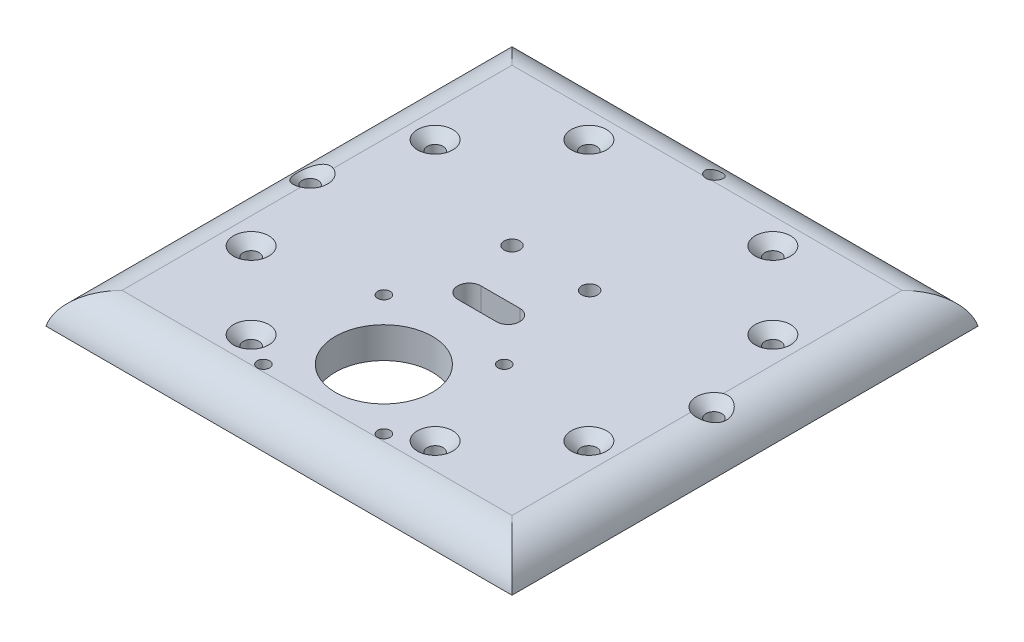
SolidWorks part; units mm, degrees
ref_plane "Front Plane" through (0, 0, 0) normal (0, 0, 1) x (1, 0, 0)
ref_plane "Top Plane" through (0, 0, 0) normal (0, 1, 0) x (1, 0, 0)
ref_plane "Right Plane" through (0, 0, 0) normal (1, 0, 0) x (0, 0, -1)
sketch "Sketch1" plane through (0, 0, 0) normal (0, 1, 0) x (1, 0, 0)
  line L0 (0, 0) -> (33.616, 0) construction
  line L8 (0, 0) -> (0, 37.386) construction
  line L9 (0, 37.386) -> (33.616, 0) construction
  line L18 (60, -60) -> (-60, -60)
  line L19 (60, -60) -> (60, 60)
  line L20 (60, 60) -> (-60, 60)
  line L21 (-60, -60) -> (-60, 60)
  line L22 (60, -60) -> (-60, 60) construction
  line L23 (60, 60) -> (-60, -60) construction
  circle A0 centre (0, 0) radius 60 construction
  dimension "D1" = 120
extrude "Boss-Extrude1" add sketch "Sketch1" along normal blind 8
sketch "Sketch2" plane through (0, 8, 0) normal (0, 1, 0) x (1, 0, 0)
  line L1 (15.5, -48.5) -> (-15.5, -48.5) construction
  line L2 (15.5, -48.5) -> (15.5, -17.5) construction
  line L3 (15.5, -17.5) -> (-15.5, -17.5) construction
  line L4 (-15.5, -48.5) -> (-15.5, -17.5) construction
  line L5 (15.5, -48.5) -> (-15.5, -17.5) construction
  line L6 (15.5, -17.5) -> (-15.5, -48.5) construction
  circle A0 centre (0, -33) radius 12.5
  circle A1 centre (-15.5, -48.5) radius 1.6
  circle A2 centre (15.5, -48.5) radius 1.6
  circle A3 centre (15.5, -17.5) radius 1.6
  circle A4 centre (-15.5, -17.5) radius 1.6
  dimension "D1" = 25
  dimension "D5" = 3.2
  dimension "D6" = 3.2
  dimension "D7" = 3.2
  dimension "D8" = 3.2
  dimension "D2" = 33
  dimension "D3" = 31
  dimension "D4" = 31
extrude "Cut-Extrude1" cut sketch "Sketch2" against normal through all
sketch "Sketch3" plane through (0, 8, 0) normal (0, 1, 0) x (1, 0, 0)
  line L0 (0, 0) -> (0, -60) construction
  line L1 (0, 0) -> (-33.5876, -33.5876) construction
  line L2 (-9.8995, 9.8995) -> (-43.4871, -23.6881) construction
  line L3 (9.8995, -9.8995) -> (-23.6881, -43.4871) construction
  circle A0 centre (0, 0) radius 60 construction
  circle A1 centre (-33.5876, -33.5876) radius 5 construction
  circle A2 centre (-43.4871, -23.6881) radius 2.05
  circle A3 centre (-23.6881, -43.4871) radius 2.05
  dimension "D5" = 4.1
  dimension "D6" = 4.1
  dimension "D7" = 10
  dimension "D1" = 45
  dimension "D2" = 47.5
  dimension "D3" = 14
  dimension "D4" = 14
extrude "Cut-Extrude2" cut sketch "Sketch3" against normal through all contours A2 | A3
pattern_circular "CirPattern1" count 4 over 360 about axis through (0, 0, 0) along (0, 1, 0) of "Cut-Extrude2"
sketch "Sketch4" plane through (0, 8, 0) normal (0, 1, 0) x (1, 0, 0)
  circle A0 centre (-52, 0) radius 2.05
  circle A1 centre (52, 0) radius 2.05
  circle A2 centre (0, 52) radius 2.05
  dimension "D3" = 4.1
  dimension "D4" = 4.1
  dimension "D6" = 4.1
  dimension "D1" = 52
  dimension "D2" = 52
  dimension "D5" = 52
extrude "Cut-Extrude3" cut sketch "Sketch4" against normal through all
sketch "Sketch5" plane through (0, 8, 0) normal (0, 1, 0) x (1, 0, 0)
  line L0 (-5, -6) -> (5, -6) construction
  line L1 (-5, -3) -> (5, -3)
  line L2 (-5, -9) -> (5, -9)
  circle A0 centre (-10, 10) radius 2.05
  circle A1 centre (10, 10) radius 2.05
  arc A2 (-5, -3) -> (-5, -9) centre (-5, -6) ccw
  arc A3 (5, -9) -> (5, -3) centre (5, -6) ccw
  point P6 (0, -6)
  dimension "D1" = 3
  dimension "D2" = 4.1
  dimension "D3" = 4.1
  dimension "D4" = 13
  dimension "D5" = 3
  dimension "D6" = 10
  dimension "D7" = 10
  dimension "D8" = 10
extrude "Cut-Extrude4" cut sketch "Sketch5" against normal through all
sketch "Sketch6" plane through (0, 0, 0) normal (0, -1, 0) x (1, 0, 0)
  line L1 (0, -38) -> (8, -38)
  line L2 (0, -38) -> (0, -18)
  line L3 (0, -18) -> (8, -18)
  line L4 (8, -38) -> (8, -18)
  line L5 (0, -38) -> (8, -18) construction
  line L6 (0, -18) -> (8, -38) construction
  point P0 (4, -28)
  dimension "D1" = 20
  dimension "D2" = 8
  dimension "D3" = 18
extrude "Boss-Extrude2" add sketch "Sketch6" along normal blind 18 contours L3 L4 L1 L2
chamfer "Chamfer1" distance 5 angle 45 1 edges at (8, 0, -28)
sketch "Sketch7" plane through (8, 0, 0) normal (1, 0, 0) x (0, 0, -1)
  line L0 (38, -18) -> (18, -18) construction
  line L1 (38, -18) -> (38, -5) construction
  circle A0 centre (23.25, -10.5) radius 1.6
  circle A1 centre (32.75, -10.5) radius 1.6
  dimension "D1" = 7.5
  dimension "D2" = 3.2
  dimension "D3" = 3.2
  dimension "D4" = 9.5
  dimension "D5" = 5.25
extrude "Cut-Extrude5" cut sketch "Sketch7" against normal through all
hole_wizard "CSK for M4 Countersunk Flat Head Screw1" positions "3DSketch1" profile "Sketch9" countersink size "M4" standard "ISO"
sketch3d "3DSketch1"
  line L0 (-52, 0, 0) -> (-52, 8, 0) construction
  line L1 (-43.4871, 0, 23.6881) -> (-43.4871, 8, 23.6881) construction
  line L2 (-23.6881, 0, 43.4871) -> (-23.6881, 8, 43.4871) construction
  line L3 (23.6881, 0, 43.4871) -> (23.6881, 8, 43.4871) construction
  line L4 (43.4871, 0, 23.6881) -> (43.4871, 8, 23.6881) construction
  line L5 (52, 0, 0) -> (52, 8, 0) construction
  line L6 (43.4871, 0, -23.6881) -> (43.4871, 8, -23.6881) construction
  line L7 (23.6881, 0, -43.4871) -> (23.6881, 8, -43.4871) construction
  line L8 (-23.6881, 0, -43.4871) -> (-23.6881, 8, -43.4871) construction
  line L9 (-43.4871, 0, -23.6881) -> (-43.4871, 8, -23.6881) construction
  point P0 (-52, 8, 0)
  point P4 (-43.4871, 8, 23.6881)
  point P8 (-23.6881, 8, 43.4871)
  point P12 (23.6881, 8, 43.4871)
  point P16 (43.4871, 8, 23.6881)
  point P20 (52, 8, 0)
  point P24 (43.4871, 8, -23.6881)
  point P28 (23.6881, 8, -43.4871)
  point P32 (-23.6881, 8, -43.4871)
  point P36 (-43.4871, 8, -23.6881)
sketch "Sketch9" plane through (-52, 8, 0) normal (1, 0, 0) x (0, 0, 1)
  line L0 (0, 0) -> (0, 9.2308)
  line L1 (0, 9.2308) -> (2.05, 7.999)
  line L2 (2.05, 7.999) -> (2.05, 2.5)
  line L3 (2.05, 2.5) -> (4.55, 0)
  line L5 (4.55, 0) -> (0, 0)
  line L6 (-2.05, 2.5) -> (-4.55, 0) construction
  line L10 (0, 9.2308) -> (-2.05, 7.999) construction
  line L11 (0, -6.35) -> (0, 107.95) construction
  dimension "Hole Dia." = 4.1
  dimension "Hole Depth" = 7.999
  dimension "Near C'Sink Dia." = 9.1
  dimension "Near C'Sink Angle" = 90
  dimension "Drill Angle" = 118
fillet "Fillet1" radius 10 4 edges at (0, 8, -60) (60, 8, 0) (-60, 8, 0) (0, 8, 60)
